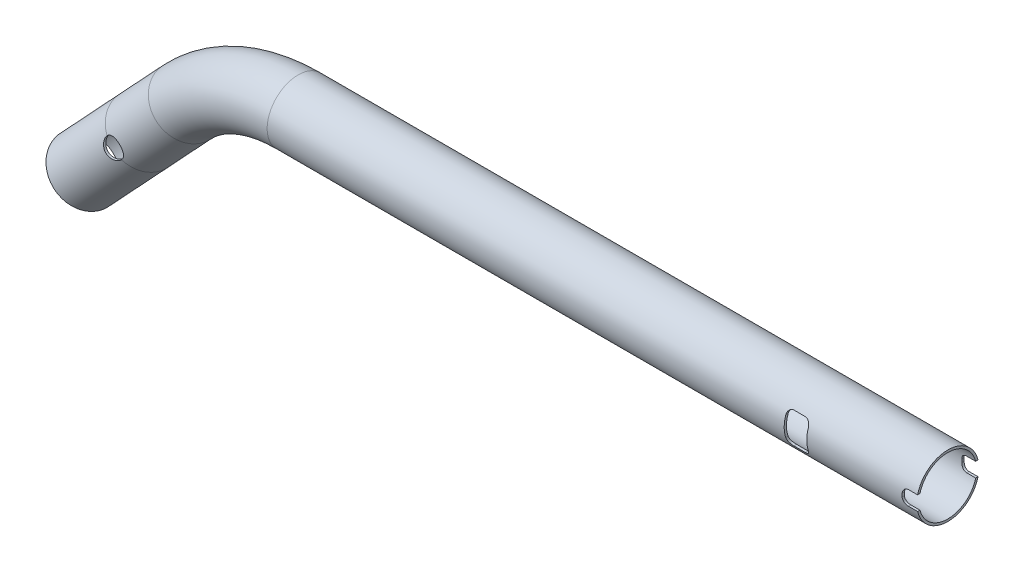
SolidWorks part; units mm, degrees
ref_plane "Front Plane" through (0, 0, 0) normal (0, 0, 1) x (1, 0, 0)
ref_plane "Top Plane" through (0, 0, 0) normal (0, 1, 0) x (1, 0, 0)
ref_plane "Right Plane" through (0, 0, 0) normal (1, 0, 0) x (0, 0, -1)
sketch "Sketch1" plane through (0, 0, 0) normal (0, 0, 1) x (1, 0, 0)
  line L0 (-93.6265, 0) -> (93.6265, 0)
  line L1 (-133.1196, -17.1721) -> (-148.3735, -33.53)
  line L2 (93.6265, 0) -> (136.6265, 0)
  line L3 (-148.3735, -33.53) -> (-169.3735, -56.0497)
  arc A0 (-93.6265, 0) -> (-133.1196, -17.1721) centre (-93.6265, -54) ccw
  point P4 (0, 0)
  point P10 (-148.3735, -33.53)
  dimension "D2" = 54
  dimension "D7" = 306
  dimension "D1" = 47
  dimension "D3" = 33.53
  dimension "D4" = 242
  dimension "D5" = 43
  dimension "D6" = 47
ref_plane "Plane1" through (93.6265, 0, 0) normal (1, 0, 0) x (0, 0, -1)
sketch "Sketch3" plane through (93.6265, 0, 0) normal (1, 0, 0) x (0, 0, -1)
  circle A0 centre (0, 0) radius 11
  circle A1 centre (0, 0) radius 10.2
  dimension "D1" = 0.8
  dimension "D2" = 22
sweep "Sweep2" add profiles "Sketch3" path "Sketch1"
ref_axis "Axis1" through (136.6265, 0, 0) along (-1, 0, 0)
ref_axis "Axis2" through (-125.6358, -9.1468, 0) along (-0.682, -0.7314, 0)
sketch "Sketch4" plane through (0, 0, 0) normal (0, 0, 1) x (1, 0, 0)
  line L0 (-156.4184, -26.028) -> (-140.3287, -41.032) construction
  line L1 (93.6265, -101.4635) -> (93.6265, 101.4635) construction
  line L2 (136.6265, 0) -> (93.6265, 0) construction
  line L3 (136.6265, -11) -> (136.6265, 11) construction
  line L4 (136.6265, 0) -> (-93.6265, 0) construction
  line L6 (91.6265, -5.5) -> (95.6265, -5.5)
  line L7 (89.6265, -3.5) -> (89.6265, 3.5)
  line L8 (91.6265, 5.5) -> (95.6265, 5.5)
  line L9 (97.6265, -3.5) -> (97.6265, 3.5)
  line L10 (89.6265, -5.5) -> (97.6265, 5.5) construction
  line L11 (89.6265, 5.5) -> (97.6265, -5.5) construction
  circle A0 centre (-148.3735, -33.53) radius 3.5
  arc A1 (91.6265, -5.5) -> (89.6265, -3.5) centre (91.6265, -3.5) cw
  arc A2 (97.6265, -3.5) -> (95.6265, -5.5) centre (95.6265, -3.5) cw
  arc A3 (95.6265, 5.5) -> (97.6265, 3.5) centre (95.6265, 3.5) cw
  arc A4 (91.6265, 5.5) -> (89.6265, 3.5) centre (91.6265, 3.5) ccw
  dimension "D1" = 43
  dimension "D4" = 2
  dimension "D6" = 7
  dimension "D2" = 8
  dimension "D3" = 11
extrude "Cut-Extrude1" cut sketch "Sketch4" along normal up to next
sketch "Sketch5" plane through (0, 0, 0) normal (0, 0, 1) x (1, 0, 0)
  line L0 (-155.8334, -26.5736) -> (-140.9137, -40.4864) construction
  circle A0 centre (-148.3735, -33.53) radius 3.3
extrude "Cut-Extrude2" cut sketch "Sketch5" against normal through all
sketch "Sketch6" plane through (0, 0, 0) normal (0, 0, 1) x (1, 0, 0)
  line L4 (136.7002, 2.5547) -> (136.6265, -2.5547)
  line L5 (136.6265, -11) -> (136.6265, 11) construction
  line L6 (136.6265, -2.5547) -> (133.4265, -2.5547)
  line L7 (131.4265, -0.5547) -> (131.4265, 0.5547)
  line L8 (133.4265, 2.5547) -> (136.7002, 2.5547)
  arc A2 (133.4265, -2.5547) -> (131.4265, -0.5547) centre (133.4265, -0.5547) cw
  arc A3 (133.4265, 2.5547) -> (131.4265, 0.5547) centre (133.4265, 0.5547) ccw
  point P7 (136.6633, 0)
  point P11 (131.4265, -2.5547)
  dimension "D1" = 5.11
  dimension "D3" = 2
  dimension "D2" = 5.2
extrude "Cut-Extrude3" cut sketch "Sketch6" against normal through all and the other way through all
